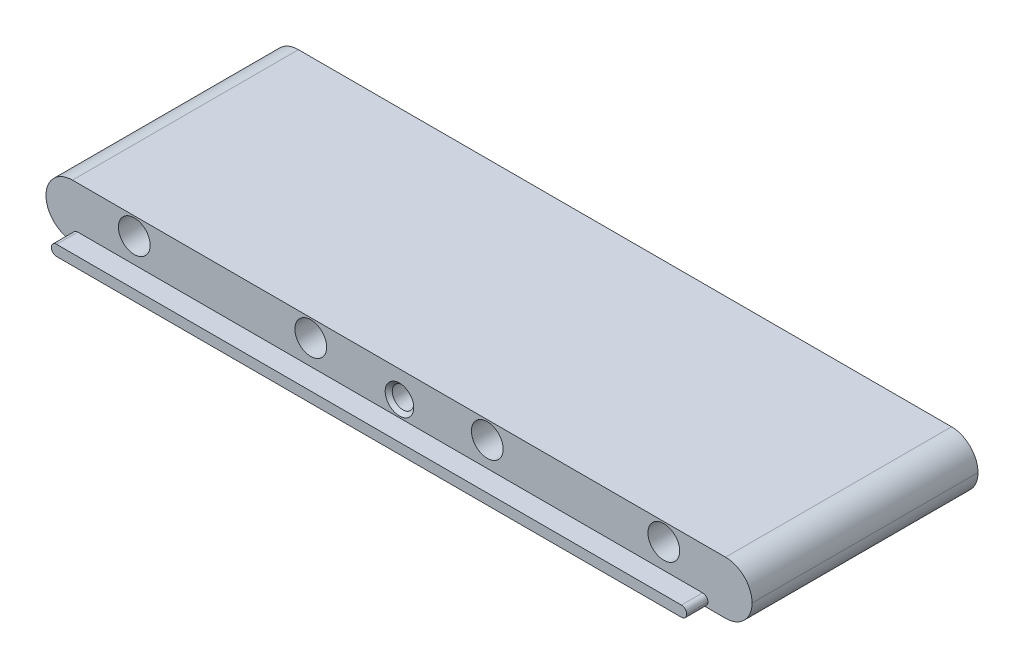
SolidWorks part; units mm, degrees
ref_plane "Front Plane" through (0, 0, 0) normal (0, 0, 1) x (1, 0, 0)
ref_plane "Top Plane" through (0, 0, 0) normal (0, 1, 0) x (1, 0, 0)
ref_plane "Right Plane" through (0, 0, 0) normal (1, 0, 0) x (0, 0, -1)
sketch "Sketch1" plane through (0, 0, 0) normal (0, 0, 1) x (1, 0, 0)
  line L1 (-100, -7.5) -> (100, -7.5)
  line L2 (-100, -7.5) -> (-100, 7.5)
  line L3 (-100, 7.5) -> (100, 7.5)
  line L4 (100, -7.5) -> (100, 7.5)
  line L5 (-100, -7.5) -> (100, 7.5) construction
  line L6 (-100, 7.5) -> (100, -7.5) construction
  circle A0 centre (75, 2.5) radius 2.6
  circle A1 centre (25, 2.5) radius 2.6
  circle A2 centre (-25, 2.5) radius 2.6
  circle A3 centre (-75, 2.5) radius 2.6
  point P0 (0, 0)
  dimension "D3" = 5.2
  dimension "D5" = 5
  dimension "D1" = 15
  dimension "D2" = 200
  dimension "D4" = 75
  dimension "D7" = 25
  dimension "D6" = 4
extrude "Boss-Extrude1" add sketch "Sketch1" along normal blind 64
sketch "Sketch2" plane through (0, 0, 64) normal (0, 0, 1) x (1, 0, 0)
  circle A0 centre (-75, 2.5) radius 4.5
  circle A1 centre (-25, 2.5) radius 4.5
  circle A2 centre (25, 2.5) radius 4.5
  circle A3 centre (75, 2.5) radius 4.5
  dimension "D1" = 9
extrude "Cut-Extrude1" cut sketch "Sketch2" against normal offset from surface (57 mm away) 7 up to face at (-22.4, 2.5, 0)
fillet "Fillet3" radius 7.5 4 edges at (100, 7.5, 32) (100, -7.5, 32) (-100, 7.5, 32) (-100, -7.5, 32)
sketch "Sketch3" plane through (0, 0, 64) normal (0, 0, 1) x (1, 0, 0)
  line L1 (-92.5, -7.5) -> (87.5, -7.5)
  line L2 (-92.5, -7.5) -> (-92.5, -4.5)
  line L3 (-92.5, -4.5) -> (87.5, -4.5)
  line L4 (87.5, -7.5) -> (87.5, -4.5)
  dimension "D1" = 180
  dimension "D2" = 3
extrude "Boss-Extrude2" add sketch "Sketch3" along normal blind 6
fillet "Fillet4" radius 1.5 4 edges at (87.5, -4.5, 67) (87.5, -7.5, 67) (-92.5, -7.5, 67) (-92.5, -4.5, 67)
sketch "Sketch4" plane through (0, 0, 64) normal (0, 0, 1) x (1, 0, 0)
  line L1 (92.5, 7.5) -> (-92.5, 7.5) construction
  circle A1 centre (0.1253, 0) radius 3.05
  circle A3 centre (25, 2.5) radius 2.6 construction
  dimension "D1" = 7.5
  dimension "D3" = 6.1
  dimension "D2" = 25
extrude "Cut-Extrude2" cut sketch "Sketch4" against normal blind 8
chamfer "Chamfer1" distance 1 angle 45 1 edges at (3.1753, 0, 64)
